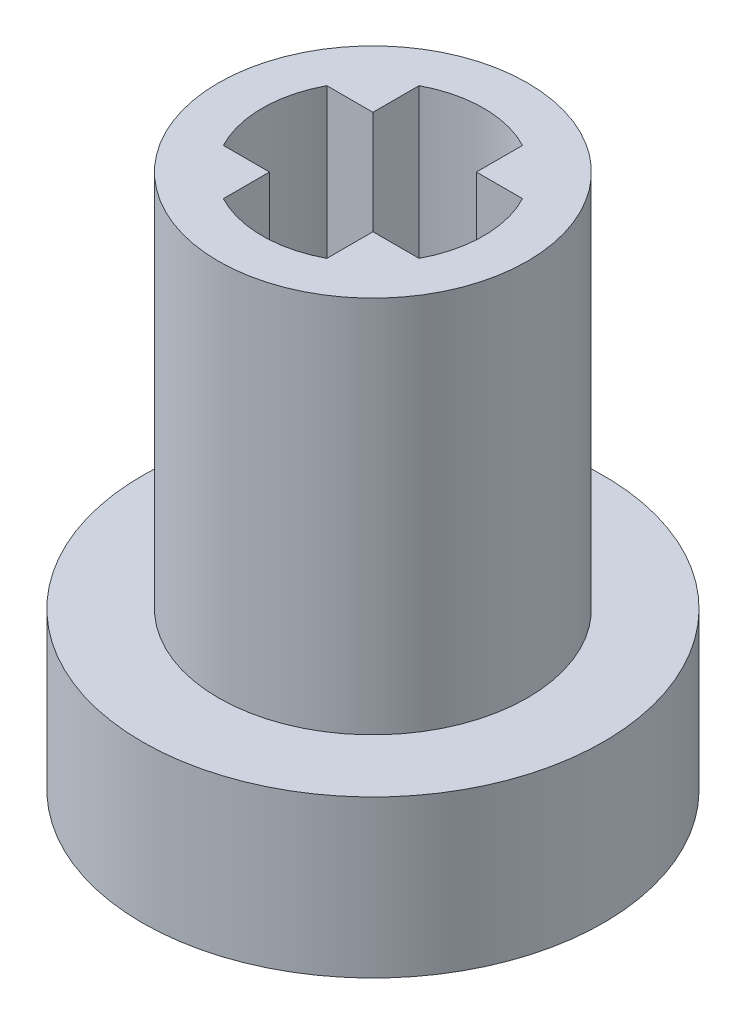
SolidWorks part; units mm, degrees
ref_plane "前视基准面" through (0, 0, 0) normal (0, 0, 1) x (1, 0, 0)
ref_plane "上视基准面" through (0, 0, 0) normal (0, 1, 0) x (1, 0, 0)
ref_plane "右视基准面" through (0, 0, 0) normal (1, 0, 0) x (0, 0, -1)
other "Configuration Table"
sketch "草图1" plane through (0, 0, 0) normal (0, 1, 0) x (1, 0, 0)
  circle A0 centre (0, 0) radius 2.55
  circle A2 centre (0, 0) radius 5
  dimension "D1" = 5.1
  dimension "D2" = 10
extrude "凸台-拉伸1" add sketch "草图1" along normal blind 3.4 contours A2
extrude "切除-拉伸1" cut sketch "草图1<3>" along normal blind 2.4 contours A0 region at (0, 0, 0)
sketch "草图1<3>" plane through (0, 0, 0) normal (0, 1, 0) x (1, 0, 0) same geometry as "草图1"
sketch "草图2" plane through (0, 3.4, 0) normal (0, 1, 0) x (1, 0, 0)
  line L1 (-1.1217, 2.1217) -> (1.1217, 2.1217)
  line L2 (-1.1217, 2.1217) -> (-1.1217, -2.1217)
  line L3 (-1.1217, -2.1217) -> (1.1217, -2.1217)
  line L4 (1.1217, 2.1217) -> (1.1217, -2.1217)
  line L5 (-1.1217, 2.1217) -> (1.1217, -2.1217) construction
  line L6 (-1.1217, -2.1217) -> (1.1217, 2.1217) construction
  line L7 (-2.1217, -1.1217) -> (2.1217, -1.1217)
  line L8 (-2.1217, -1.1217) -> (-2.1217, 1.1217)
  line L9 (-2.1217, 1.1217) -> (2.1217, 1.1217)
  line L10 (2.1217, -1.1217) -> (2.1217, 1.1217)
  line L11 (-2.1217, -1.1217) -> (2.1217, 1.1217) construction
  line L12 (-2.1217, 1.1217) -> (2.1217, -1.1217) construction
  circle A0 centre (0, 0) radius 2.4
  circle A1 centre (0, 0) radius 3.35
  point P12 (0, 0)
  point P13 (0, 0)
  point P14 (-2.086, 2.6213)
  dimension "D1" = 4.8
  dimension "D2" = 6.7
  dimension "D3" = 1
extrude "凸台-拉伸2" add sketch "草图2" along normal blind 0.2 contours A1
extrude "凸台-拉伸3" add sketch "草图2<3>" along normal blind 8 from surface contours A1 A0 | L2 A0 L9 | L9 A0 L4 | L7 A0 L2 | L4 A0 L7 region at (-1.4881, 3.4, -1.4881) region at (1.4881, 3.4, -1.4881) region at (-1.4881, 3.4, 1.4881) region at (1.4881, 3.4, 1.4881) region at (-3.2552, 3.4, 0) starting at face at (0, 3.6, 3.35)
sketch "草图2<3>" plane through (0, 3.4, 0) normal (0, 1, 0) x (1, 0, 0) same geometry as "草图2"
